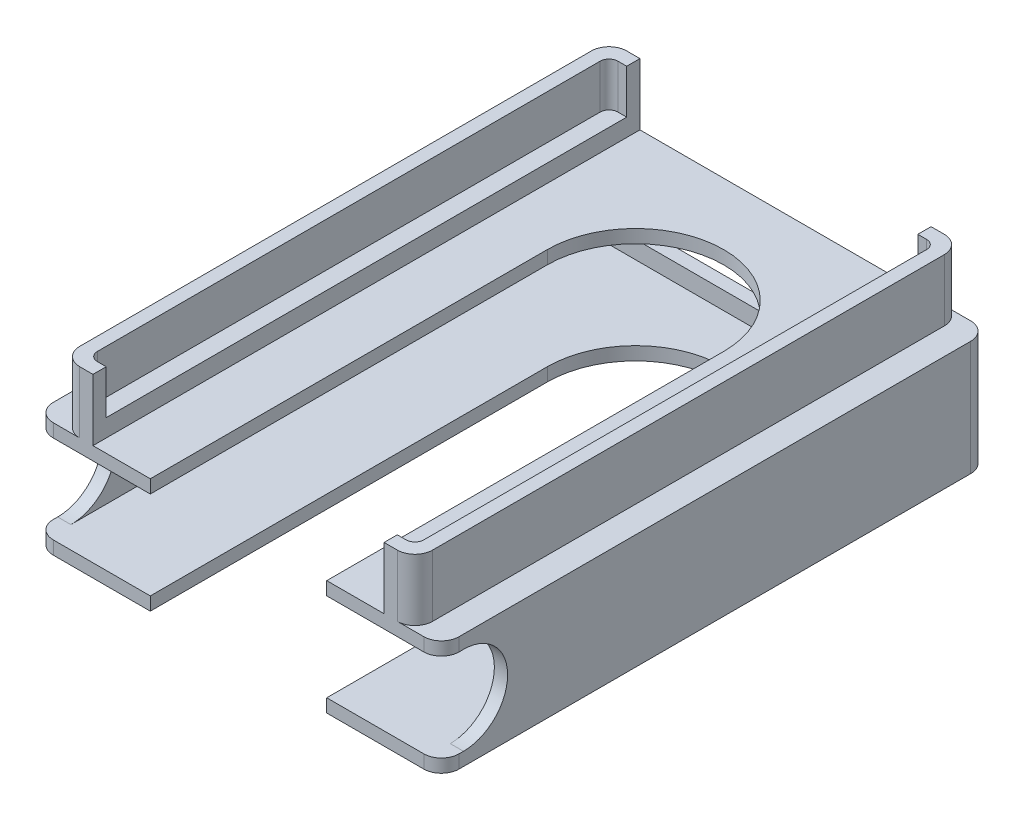
SolidWorks part; units mm, degrees
ref_plane "Front Plane" through (0, 0, 0) normal (0, 0, 1) x (1, 0, 0)
ref_plane "Top Plane" through (0, 0, 0) normal (0, 1, 0) x (1, 0, 0)
ref_plane "Right Plane" through (0, 0, 0) normal (1, 0, 0) x (0, 0, -1)
sketch "battery-base" plane through (0, 0, 0) normal (0, 1, 0) x (1, 0, 0)
  line L0 (-10.75, -13.5) -> (-11.5, -13.5)
  line L1 (-10.5, 16.25) -> (10.5, 16.25)
  line L2 (11.5, 15.25) -> (11.5, -13.75)
  line L3 (10.5, -14.75) -> (-10.5, -14.75)
  line L4 (-11.5, 15.25) -> (-11.5, -13.75)
  line L7 (10.25, 15.5) -> (-10.25, 15.5)
  line L8 (10.75, 15) -> (10.75, -13.5)
  line L9 (10.25, -14) -> (-10.25, -14)
  line L10 (-10.75, 15) -> (-10.75, -13.5)
  line L13 (10.75, -13.5) -> (11.5, -13.5)
  arc A0 (-11.5, -13.75) -> (-10.5, -14.75) centre (-10.5, -13.75) ccw
  arc A1 (11.5, -13.75) -> (10.5, -14.75) centre (10.5, -13.75) cw
  arc A2 (11.5, 15.25) -> (10.5, 16.25) centre (10.5, 15.25) ccw
  arc A3 (-11.5, 15.25) -> (-10.5, 16.25) centre (-10.5, 15.25) cw
  arc A4 (-10.75, 15) -> (-10.25, 15.5) centre (-10.25, 15) cw
  arc A5 (-10.75, -13.5) -> (-10.25, -14) centre (-10.25, -13.5) ccw
  arc A6 (10.25, -14) -> (10.75, -13.5) centre (10.25, -13.5) ccw
  arc A7 (10.75, 15) -> (10.25, 15.5) centre (10.25, 15) ccw
  point P0 (0, 0)
  point P6 (0, 0)
extrude "base-extrude" add sketch "battery-base" along normal blind 0.75 contours L3 A0 L4 A3 L1 A2 L2 A1
extrude "sidewall-extrude" add sketch "battery-base<12>" along normal blind 5.75 contours A7 L8 L13 L2 A2 L1 A3 L4 L0 L10 A4 L7 region at (-11.125, 0, 13.124)
sketch "battery-base<12>" plane through (0, 0, 0) normal (0, 1, 0) x (1, 0, 0) same geometry as "battery-base"
extrude "top-extrude" add sketch "battery-base<13>" along normal blind 0.75 from offset 5.75 contours L8 A7 L7 A4 L10 A5 L9 A6 | A6 L9 A5 L0 L4 A0 L3 A1 L2 L13 | A7 L8 L13 L2 A2 L1 A3 L4 L0 L10 A4 L7 region at (0, 0, 14.3418) region at (-11.125, 0, 13.124) region at (0, 0, -0.75)
sketch "battery-base<13>" plane through (0, 0, 0) normal (0, 1, 0) x (1, 0, 0) same geometry as "battery-base"
sketch "round-cut" plane through (11.5, 0, 0) normal (1, 0, 0) x (0, 0, -1)
  line L0 (-13.5, 5.75) -> (-13.5, 0.75) construction
  line L1 (-13.5, 5.75) -> (-13.75, 5.75) construction
  arc A0 (-13.5, 0.75) -> (-13.5, 5.75) centre (-13.5, 3.25) ccw
extrude "Cut-Extrude1" cut sketch "round-cut" against normal through all and the other way through all
sketch "PCB-support" plane through (0, 6.5, 0) normal (0, 1, 0) x (1, 0, 0)
  line L0 (-8.25, -14) -> (-8.25, 15.5)
  line L1 (-8.75, 15.5) -> (8.75, 15.5)
  line L2 (-9.25, 15) -> (-9.25, -13.5)
  line L3 (-8.75, -14) -> (8.75, -14)
  line L4 (9.25, 15) -> (9.25, -13.5)
  line L5 (-9, 16.25) -> (9, 16.25)
  line L6 (-10, 15.25) -> (-10, -13.75)
  line L7 (-9, -14.75) -> (9, -14.75)
  line L8 (10, 15.25) -> (10, -13.75)
  line L9 (8.25, -14) -> (8.25, 15.5)
  line L10 (-8.25, -14) -> (-8.25, -14.75)
  line L11 (8.25, -14) -> (8.25, -14.75)
  line L12 (-8.25, 15.5) -> (-8.25, 16.25)
  line L13 (8.25, 15.5) -> (8.25, 16.25)
  arc A0 (-10, -13.75) -> (-9, -14.75) centre (-9, -13.75) ccw
  arc A1 (9, -14.75) -> (10, -13.75) centre (9, -13.75) ccw
  arc A2 (10, 15.25) -> (9, 16.25) centre (9, 15.25) ccw
  arc A3 (-9, 16.25) -> (-10, 15.25) centre (-9, 15.25) ccw
  arc A4 (-9.25, -13.5) -> (-8.75, -14) centre (-8.75, -13.5) ccw
  arc A5 (8.75, -14) -> (9.25, -13.5) centre (8.75, -13.5) ccw
  arc A6 (9.25, 15) -> (8.75, 15.5) centre (8.75, 15) ccw
  arc A7 (-8.75, 15.5) -> (-9.25, 15) centre (-8.75, 15) ccw
  line M4 (-10.5, -14.75) -> (10.5, -14.75)
  line M8 (10.5, 16.25) -> (-10.5, 16.25)
extrude "PCB-support-extrude" add sketch "PCB-support" along normal blind 1 contours L1 A7 L2 A4 L3 L0 | L4 A6 L1 L9 L3 A5 region at (-8.7486, 6.5, -0.75) region at (8.7486, 6.5, -0.75)
extrude "PCB-rim-extrude" add sketch "PCB-support<3>" along normal blind 3.5 contours A7 L1 A6 L4 A5 L3 L11 A1 L8 A2 A3 L6 A0 L10 A4 L2 M4 M8 | A7 L1 L12 L5 A3 L6 A0 L10 L3 A4 L2 M4 region at (-9.5665, 6.5, -0.75) region at (9.5665, 6.5, -0.75)
sketch "PCB-support<3>" plane through (0, 6.5, 0) normal (0, 1, 0) x (1, 0, 0) same geometry as "PCB-support"
sketch "cut-away" plane through (0, 6.5, 0) normal (0, 1, 0) x (1, 0, 0)
  line L0 (-5, 7.75) -> (-5, -14.75)
  line L1 (8.25, -14.75) -> (-8.25, -14.75) construction
  line L2 (5, 7.75) -> (5, -14.75)
  line L3 (5, -14.75) -> (-5, -14.75)
  arc A0 (-5, 7.75) -> (5, 7.75) centre (0, 7.75) cw
extrude "Cut-Extrude2" cut sketch "cut-away" against normal through all
sketch "Sketch7" plane through (0, 0, -16.25) normal (0, 0, -1) x (-1, 0, 0)
  line L0 (8.5849, 3.25) -> (-8.5849, 3.25) construction
  line L1 (8.5849, 1.75) -> (-8.5849, 1.75)
  line L2 (8.5849, 4.75) -> (-8.5849, 4.75)
  arc A0 (8.5849, 1.75) -> (8.5849, 4.75) centre (8.5849, 3.25) ccw
  arc A1 (-8.5849, 4.75) -> (-8.5849, 1.75) centre (-8.5849, 3.25) ccw
  point P2 (0, 3.25)
extrude "Cut-Extrude3" cut sketch "Sketch7" against normal blind 3.5
